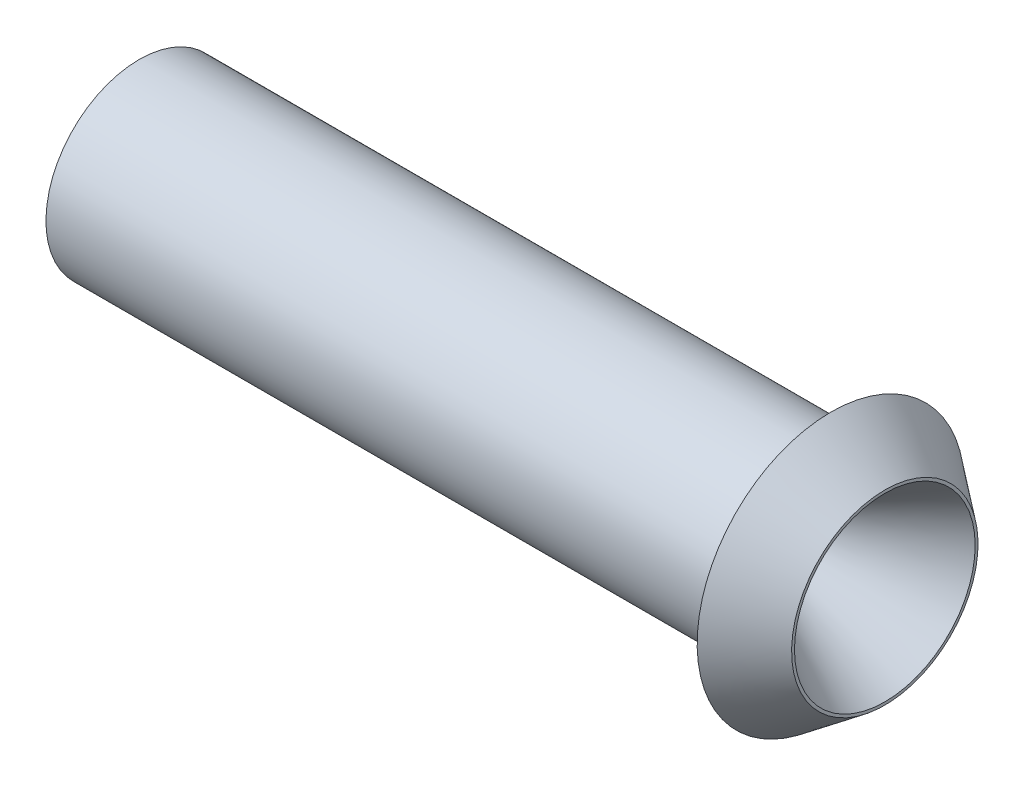
SolidWorks part; units mm, degrees
material "AISI 316 Annealed Stainless Steel Bar (SS)"
ref_plane "Front Plane" through (0, 0, 0) normal (0, 0, 1) x (1, 0, 0)
ref_plane "Top Plane" through (0, 0, 0) normal (0, 1, 0) x (1, 0, 0)
ref_plane "Right Plane" through (0, 0, 0) normal (1, 0, 0) x (0, 0, -1)
sketch "Sketch1" plane through (0, 0, 0) normal (0, 0, 1) x (1, 0, 0)
  line L0 (0, 0) -> (0, 8.255)
  line L1 (0, 8.255) -> (61.2594, 8.255)
  line L2 (61.2594, 8.255) -> (61.2594, 11.8491)
  line L3 (61.2594, 11.8491) -> (66.0289, 8.255)
  line L4 (66.0289, 8.255) -> (66.0289, 0)
  line L5 (66.0289, 0) -> (0, 0) construction
  line L7 (66.0289, 8.001) -> (56.0554, 2.2428)
  line L8 (56.0554, 2.2428) -> (54.7854, 2.2428)
  line L9 (54.7854, 2.2428) -> (0, 8.001)
  line L10 (0, 4.7625) -> (30.8123, 4.7625) construction
  line L11 (0, 3.175) -> (45.9163, 3.175) construction
  dimension "D1" = 16.51
  dimension "D2" = 61.2594
  dimension "D3" = 23.6982
  dimension "D4" = 37
  dimension "D5" = 0.254
  dimension "D6" = 0.254
  dimension "D7" = 30
  dimension "ID" = 4.4856
  dimension "D9" = 1.27
  dimension "D10" = 6
  dimension "D11" = 3.175
  dimension "D12" = 4.7625
  dimension "D13" = 45.9163
  dimension "D14" = 30.8123
revolve "Revolve1" add sketch "Sketch1" angle 360 about L5 region at (40.911, 6.3381, 0)
